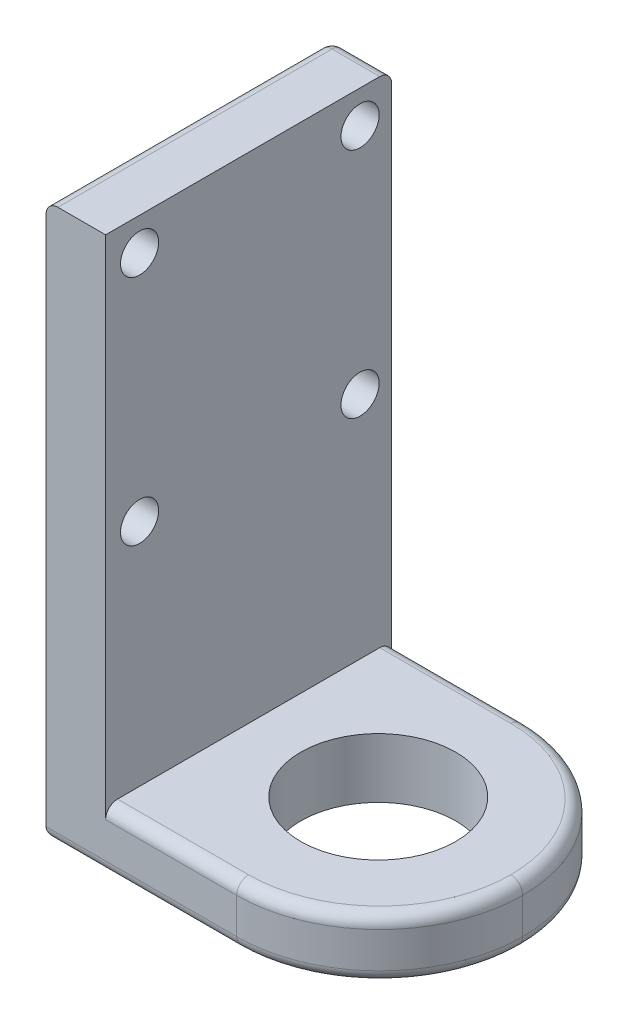
SolidWorks part; units mm, degrees
ref_plane "Alzado" through (0, 0, 0) normal (0, 0, 1) x (1, 0, 0)
ref_plane "Planta" through (0, 0, 0) normal (0, 1, 0) x (1, 0, 0)
ref_plane "Vista lateral" through (0, 0, 0) normal (1, 0, 0) x (0, 0, -1)
sketch "Croquis1" plane through (-29.8231, 0, 0) normal (-1, 0, 0) x (0, 0, 1)
  line L0 (-22.6551, 41.0126) -> (-45.8551, 41.0126) construction
  line L1 (-45.8551, 16.0126) -> (-22.6551, 16.0126) construction
  line L2 (-22.6551, 41.0126) -> (-45.8551, 41.0126) construction
  line L3 (-45.8551, 16.0126) -> (-22.6551, 16.0126) construction
  line L4 (-34.7551, 41.0126) -> (-34.7551, 16.0126) construction
  line L5 (-23.3551, -5.4874) -> (-46.3551, -5.4874) construction
  line L6 (-22.7551, 41.0126) -> (-46.7551, 41.0126)
  line L7 (-22.7551, 41.0126) -> (-22.7551, -5.4874)
  line L8 (-22.7551, -5.4874) -> (-46.7551, -5.4874)
  line L9 (-46.7551, 41.0126) -> (-46.7551, -5.4874)
  line L10 (-22.7551, 41.0126) -> (-46.7551, -5.4874) construction
  line L11 (-22.7551, -5.4874) -> (-46.7551, 41.0126) construction
  circle A4 centre (-44.1051, 38.2626) radius 1.6
  circle A5 centre (-25.6051, 38.2626) radius 1.6
  circle A6 centre (-25.6051, 18.7626) radius 1.6
  circle A7 centre (-44.1051, 18.7626) radius 1.6
  point P6 (-34.7551, 17.7626)
  dimension "D2" = 3.2
  dimension "D3" = 3.2
  dimension "D4" = 3.2
  dimension "D5" = 3.2
  dimension "D1" = 24
extrude "Saliente-Extruir1" add sketch "Croquis1" along normal blind 5
sketch "Croquis2" plane through (-29.8231, 0, 0) normal (1, 0, 0) x (0, 0, -1)
  line L0 (22.7551, -5.4874) -> (22.7551, 41.0126) construction
  line L1 (46.7551, -5.4874) -> (22.7551, -5.4874)
  line L2 (46.7551, -5.4874) -> (46.7551, -0.4874)
  line L3 (46.7551, -0.4874) -> (22.7551, -0.4874)
  line L4 (22.7551, -5.4874) -> (22.7551, -0.4874)
extrude "Saliente-Extruir2" add sketch "Croquis2" along normal blind 23
sketch "Croquis3" plane through (0, -5.4874, 0) normal (0, -1, 0) x (1, 0, 0)
  circle A0 centre (-19.0475, -34.8551) radius 6.5
  dimension "D1" = 13
extrude "Cortar-Extruir1" cut sketch "Croquis3" against normal up to next
fillet "Redondeo1" radius 12 2 edges at (-6.8231, -2.9874, -22.7551) (-6.8231, -2.9874, -46.7551)
fillet "Redondeo2" radius 1 10 edges at (-26.8231, -5.4874, -22.7551) (-10.3378, -5.4874, -26.2698) (-10.3378, -5.4874, -43.2404) (-10.3378, -0.4874, -26.2698) (-10.3378, -0.4874, -43.2404) (-34.8231, -5.4874, -34.7551) (-34.8231, 17.7626, -46.7551) (-26.8231, -5.4874, -46.7551)
fillet "Redondeo3" radius 1 2 edges at (-31.8231, 41.0126, -46.7551) (-34.8231, 41.0126, -34.2551)
